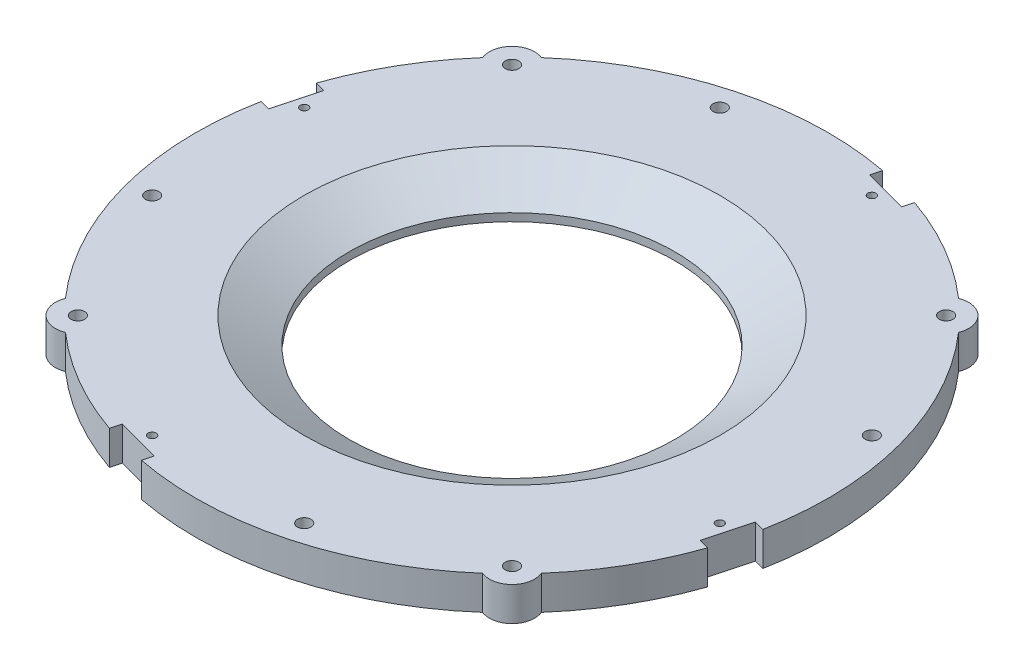
SolidWorks part; units mm, degrees
material "6061-T6 (SS)"
ref_plane "Front Plane" through (0, 0, 0) normal (0, 0, 1) x (1, 0, 0)
ref_plane "Top Plane" through (0, 0, 0) normal (0, 1, 0) x (1, 0, 0)
ref_plane "Right Plane" through (0, 0, 0) normal (1, 0, 0) x (0, 0, -1)
sketch "Sketch1" plane through (0, 0, 0) normal (0, 1, 0) x (1, 0, 0)
  line L0 (0, 88.9) -> (0, -88.9) construction
  line L1 (-88.9, 0) -> (88.9, 0) construction
  line L2 (-60.9759, -60.9759) -> (60.9759, 60.9759) construction
  line L3 (60.9759, -60.9759) -> (-60.9759, 60.9759) construction
  arc A0 (-66.8608, 58.5904) -> (-66.8608, -58.5904) centre (0, 0) ccw
  arc A1 (-58.5904, 66.8608) -> (-66.8608, 58.5904) centre (-60.9759, 60.9759) ccw
  arc A2 (66.8608, 58.5904) -> (58.5904, 66.8608) centre (60.9759, 60.9759) ccw
  arc A3 (58.5904, -66.8608) -> (66.8608, -58.5904) centre (60.9759, -60.9759) ccw
  arc A4 (-66.8608, -58.5904) -> (-58.5904, -66.8608) centre (-60.9759, -60.9759) ccw
  arc A5 (58.5904, 66.8608) -> (-58.5904, 66.8608) centre (0, 0) ccw
  arc A6 (66.8608, -58.5904) -> (66.8608, 58.5904) centre (0, 0) ccw
  arc A7 (-58.5904, -66.8608) -> (58.5904, -66.8608) centre (0, 0) ccw
  circle A8 centre (-60.9759, 60.9759) radius 1.905
  circle A9 centre (60.9759, 60.9759) radius 1.905
  circle A10 centre (60.9759, -60.9759) radius 1.905
  circle A11 centre (-60.9759, -60.9759) radius 1.905
  circle A12 centre (0, 0) radius 83.82 construction
  point P10 (0, 0)
  point P13 (0, 0)
  dimension "D1" = 177.8
  dimension "D3" = 12.7
  dimension "D4" = 3.81
  dimension "D7" = 167.64
  dimension "D2" = 90
  dimension "D5" = 45
  dimension "D6" = 172.466
extrude "Boss-Extrude1" add sketch "Sketch1" along normal blind 9.525
sketch "Sketch2" plane through (0, 9.525, 0) normal (0, 1, 0) x (1, 0, 0)
  circle A0 centre (0, 0) radius 45.72
extrude "Cut-Extrude1" cut sketch "Sketch2" against normal blind 12.7
sketch "Sketch4" plane through (0, 9.525, 0) normal (0, 1, 0) x (1, 0, 0)
  line L0 (0, 0) -> (-21.3655, 79.7372) construction
  line L2 (0, 0) -> (0, 123.2999) construction
  circle A0 centre (-21.3655, 79.7372) radius 1.905
  dimension "D1" = 3.81
  dimension "D2" = 82.55
  dimension "D3" = 15
ref_plane "Plane3" through (-62.8618, 0, -62.8618) normal (-0.7071, 0, -0.7071) x (0, -1, 0)
sketch "Sketch10" plane through (-62.8618, 0, -62.8618) normal (-0.7071, 0, -0.7071) x (0, -1, 0)
  line L0 (0, 0) -> (-9.652, 0) construction
  circle A1 centre (-4.826, 0) radius 0.6985
  dimension "D2" = 1.397
  dimension "D1" = 9.652
extrude "Cut-Extrude5" cut sketch "Sketch10" against normal blind 3.175
pattern_circular "CirPattern5" count 4 over 360 about axis through (0, 9.525, 0) along (0, 1, 0) of "Cut-Extrude5"
chamfer "Chamfer1" distance 12.7 angle 30 1 edges at (0, 9.525, 45.72) first distance on face at (0, 9.525, 45.72)
extrude "Cut-Extrude6" cut sketch "Sketch4" against normal through all
pattern_circular "CirPattern6" count 4 over 360 about axis through (0, 9.525, 0) along (0, 1, 0) of "Cut-Extrude6"
sketch "Sketch13" plane through (0, 9.525, 0) normal (0, 1, 0) x (1, 0, 0)
  line L0 (0, 0) -> (0, 128.7148) construction
  line L1 (0, 0) -> (35.1918, 131.3375) construction
  circle A0 centre (21.3655, 79.7372) radius 1.1303
  dimension "D3" = 2.2606
  dimension "D1" = 15
  dimension "D2" = 82.55
extrude "Cut-Extrude7" cut sketch "Sketch13" against normal through all
pattern_circular "CirPattern7" count 4 over 360 about axis through (0, 9.525, 0) along (0, 1, 0) of "Cut-Extrude7"
ref_plane "Plane4" through (23.009, 0, -85.8708) normal (0.2588, 0, -0.9659) x (0, -1, 0)
sketch "Sketch14" plane through (23.009, 0, -85.8708) normal (0.2588, 0, -0.9659) x (0, -1, 0)
  line L1 (1.3545, -6.35) -> (-10.5978, -6.35)
  line L2 (1.3545, -6.35) -> (1.3545, 6.35)
  line L3 (1.3545, 6.35) -> (-10.5978, 6.35)
  line L4 (-10.5978, -6.35) -> (-10.5978, 6.35)
  line L5 (1.3545, -6.35) -> (-10.5978, 6.35) construction
  line L6 (1.3545, 6.35) -> (-10.5978, -6.35) construction
  point P0 (-4.6217, 0)
  point P5 (-4.6217, 0)
  dimension "D1" = 12.7
extrude "Cut-Extrude8" cut sketch "Sketch14" against normal blind 3.175
pattern_circular "CirPattern8" count 4 over 360 about axis through (0, 9.525, 0) along (0, 1, 0) of "Cut-Extrude8"
